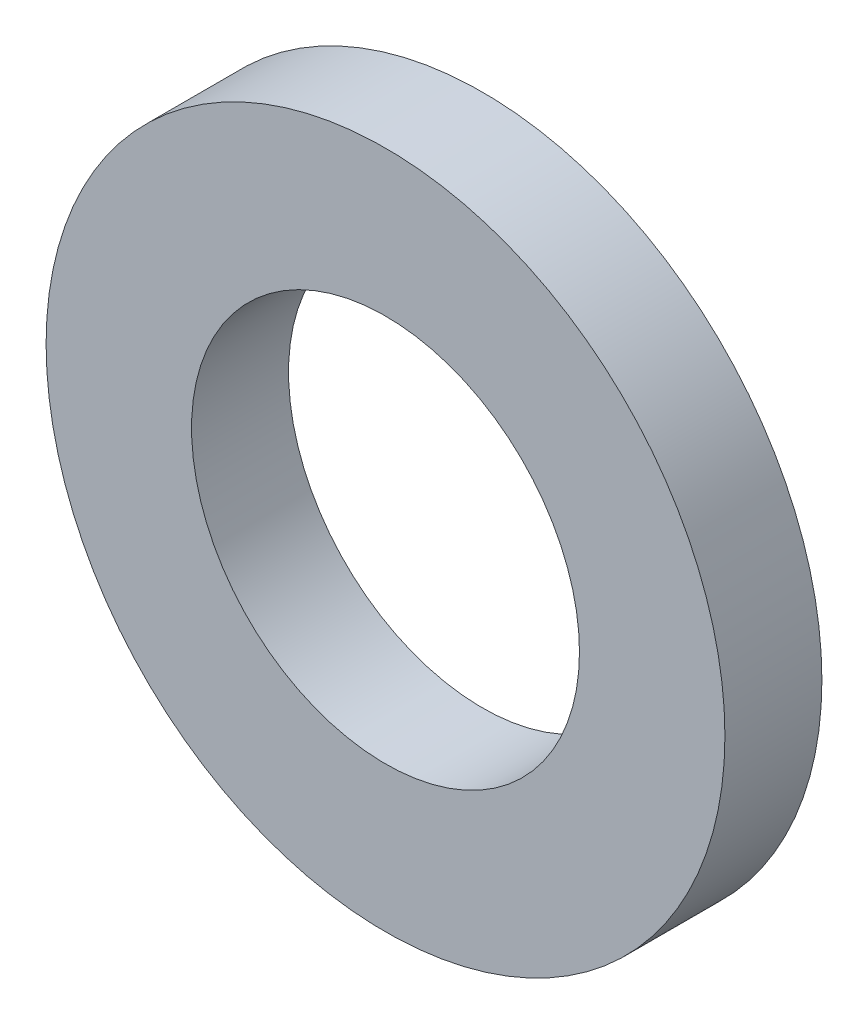
SolidWorks part; units mm, degrees
ref_plane "Front Plane" through (0, 0, 0) normal (0, 0, 1) x (1, 0, 0)
ref_plane "Top Plane" through (0, 0, 0) normal (0, 1, 0) x (1, 0, 0)
ref_plane "Right Plane" through (0, 0, 0) normal (1, 0, 0) x (0, 0, -1)
sketch "Sketch2" plane through (0, 0, 0) normal (0, 0, 1) x (1, 0, 0)
  circle A0 centre (0, 0) radius 4
  circle A1 centre (0, 0) radius 7
  dimension "D1" = 8
  dimension "D2" = 14
extrude "Boss-Extrude1" add sketch "Sketch2" along normal blind 1 and the other way blind 1
